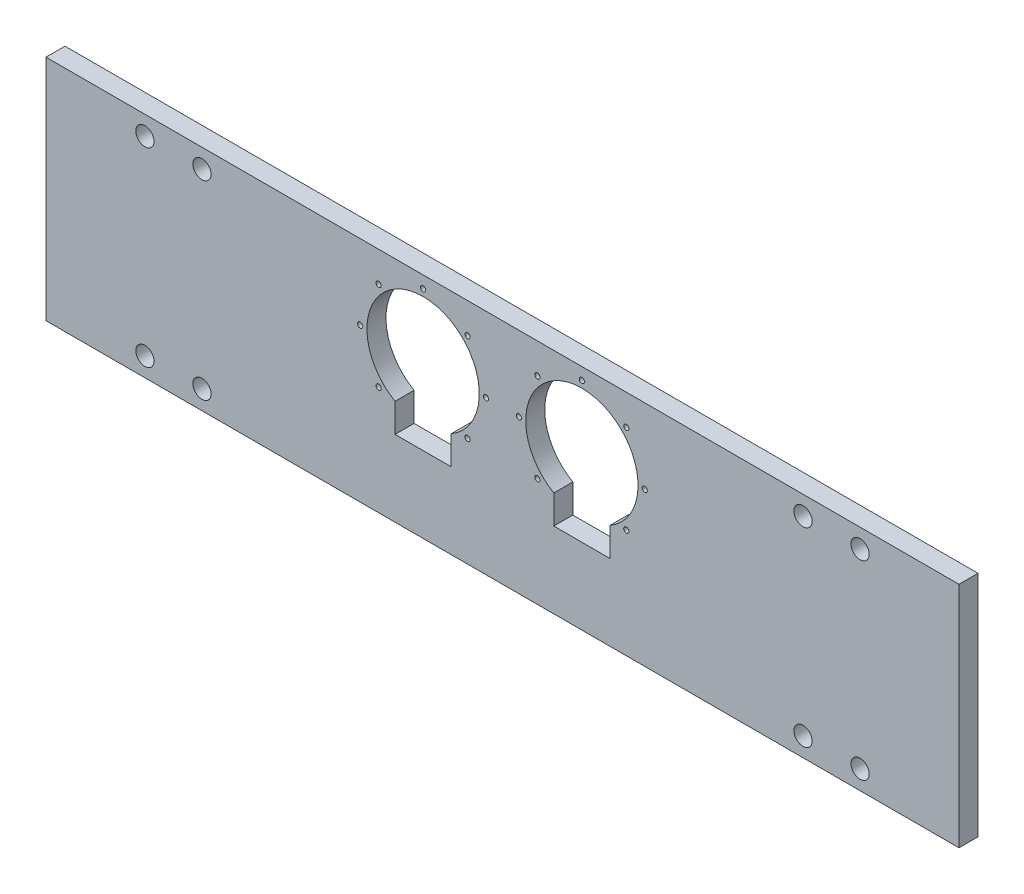
SolidWorks part; units mm, degrees
material "1060 Alloy"
ref_plane "Front Plane" through (0, 0, 0) normal (0, 0, 1) x (1, 0, 0)
ref_plane "Top Plane" through (0, 0, 0) normal (0, 1, 0) x (1, 0, 0)
ref_plane "Right Plane" through (0, 0, 0) normal (1, 0, 0) x (0, 0, -1)
sketch "Sketch1" plane through (0, 0, 0) normal (0, 0, 1) x (1, 0, 0)
  line L0 (-304.8, 0) -> (304.8, 0) construction
  line L1 (-304.8, 76.2) -> (304.8, 76.2)
  line L2 (-304.8, 76.2) -> (-304.8, -76.2)
  line L3 (-304.8, -76.2) -> (304.8, -76.2)
  line L4 (304.8, 76.2) -> (304.8, -76.2)
  line L7 (0, 76.2) -> (0, -76.2) construction
  line L8 (53, 26.2) -> (53, -11.3) construction
  line L9 (53, 26.2) -> (34.25, -6.276) construction
  line L10 (53, 26.2) -> (71.75, -6.276) construction
  line L11 (34.25, -6.276) -> (34.25, -25.4)
  line L12 (71.75, -6.276) -> (71.75, -25.4)
  line L13 (71.75, -25.4) -> (34.25, -25.4)
  line L14 (238.76, 76.2) -> (238.76, -76.2) construction
  line L15 (200.66, 76.2) -> (200.66, -76.2) construction
  line L16 (-34.25, -6.276) -> (-34.25, -25.4)
  line L17 (-71.75, -25.4) -> (-34.25, -25.4)
  line L18 (-71.75, -6.276) -> (-71.75, -25.4)
  arc A6 (71.75, -6.276) -> (34.25, -6.276) centre (53, 26.2) ccw
  circle A7 centre (53, 26.2) radius 42 construction
  circle A9 centre (82.6985, 55.8985) radius 1.746
  circle A10 centre (95, 26.2) radius 1.746
  circle A11 centre (82.6985, -3.4985) radius 1.746
  circle A13 centre (23.3015, -3.4985) radius 1.746
  circle A14 centre (11, 26.2) radius 1.746
  circle A15 centre (23.3015, 55.8985) radius 1.746
  circle A16 centre (-53, 68.2) radius 1.746
  circle A17 centre (238.76, 63.5) radius 6.096
  circle A18 centre (200.66, 63.5) radius 6.096
  circle A19 centre (238.76, -63.5) radius 6.096
  circle A20 centre (200.66, -63.5) radius 6.096
  circle A21 centre (-82.6985, -3.4985) radius 1.746
  circle A22 centre (-95, 26.2) radius 1.746
  circle A23 centre (-82.6985, 55.8985) radius 1.746
  circle A25 centre (-23.3015, 55.8985) radius 1.746
  circle A26 centre (-11, 26.2) radius 1.746
  circle A27 centre (-23.3015, -3.4985) radius 1.746
  arc A28 (-71.75, -6.276) -> (-34.25, -6.276) centre (-53, 26.2) cw
  circle A29 centre (-238.76, 63.5) radius 6.096
  circle A30 centre (-200.66, 63.5) radius 6.096
  circle A31 centre (-200.66, -63.5) radius 6.096
  circle A32 centre (-238.76, -63.5) radius 6.096
  circle A33 centre (53, 68.2) radius 1.746
  point P0 (0, 0)
  point P32 (53, 26.2)
  dimension "D6" = 75
  dimension "D7" = 84
  dimension "D15" = 12.192
  dimension "D17" = 12.192
  dimension "D8" = 3.492
  dimension "D1" = 609.6
  dimension "D2" = 152.4
  dimension "D4" = 53
  dimension "D5" = 50
  dimension "D10" = 30
  dimension "D11" = 30
  dimension "D12" = 50.8
  dimension "D13" = 66.04
  dimension "D14" = 38.1
  dimension "D16" = 12.7
  dimension "D18" = 12.7
extrude "Boss-Extrude1" add sketch "Sketch1" along normal blind 12.7
equation "\"bplate_length\"= 24in"
equation "\"bplate_height\"= 6in"
equation "\"bplate_thickness\"= 0.5in"
equation "\"motor_diameter\"= 96 / 25.4in"
equation "\"motor_clearance\"= 5 / 25.4in"
equation "\"motor_mount_hole_pattern_dia\"= 84 / 25.4in"
equation "\"motor_mount_hole_dia\"= 4 / 25.4in"
equation "\"motor_cx\"= \"motor_clearance\" + \"motor_diameter\" / 2in"
equation "\"motor_cy_top\"= \"motor_mount_hole_pattern_dia\" / 2 + \"motor_mount_hole_dia\" * 2in"
equation "\"D1@Sketch1\"=\"bplate_length\""
equation "\"D2@Sketch1\"=\"bplate_height\""
equation "\"motor_driver_cover_dia\"= 75 / 25.4in"
equation "\"D4@Sketch1\"=\"motor_cx\""
equation "\"motor_driver_cutout_clearance\"= 60deg"
equation "\"wire_cutout_clearance\"= 2in"
equation "\"connector_plate_thickness\"= 1in"
equation "\"connector_plate_hole_diameter\"= 0.5in"
equation "\"connector_plate_hole_depth\"= 1in"
equation "\"coonector_first_hole_offset\"= 1.6in"
equation "\"D14@Sketch1\"=1.5"
equation "\"D13@Sketch1\"=\"coonector_first_hole_offset\"+1in"
equation "\"D12@Sketch1\"=\"wire_cutout_clearance\""
equation "\"D16@Sketch1\"=\"connector_plate_thickness\"/2"
equation "\"D18@Sketch1\"=\"connector_plate_thickness\"/2"
equation "\"D15@Sketch1\"=\"connector_plate_hole_diameter\"- 0.02"
equation "\"D17@Sketch1\"=\"connector_plate_hole_diameter\"-0.02"
equation "\"D6@Sketch1\"=\"motor_driver_cover_dia\""
equation "\"D7@Sketch1\"=\"motor_mount_hole_pattern_dia\""
equation "\"D8@Sketch1\"=\"motor_mount_hole_dia\" - 0.02"
